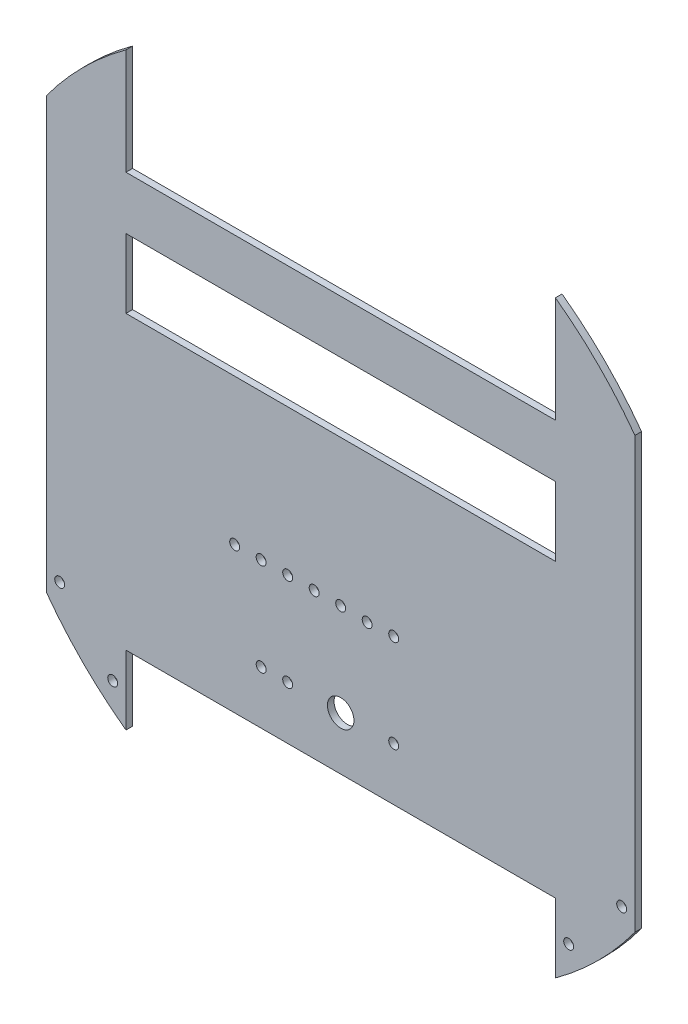
SolidWorks part; units mm, degrees
material "6061 Alloy"
ref_plane "Front Plane" through (0, 0, 0) normal (0, 0, 1) x (1, 0, 0)
ref_plane "Top Plane" through (0, 0, 0) normal (0, 1, 0) x (1, 0, 0)
ref_plane "Right Plane" through (0, 0, 0) normal (1, 0, 0) x (0, 0, -1)
sketch "Sketch1" plane through (0, 0, 0) normal (0, 0, 1) x (1, 0, 0)
  line L1 (-140.9655, 145.0225) -> (-102.8655, 145.0225)
  line L2 (-140.9655, 145.0225) -> (-140.9655, -145.0225)
  line L3 (-140.9655, -145.0225) -> (-102.8655, -145.0225)
  line L4 (-102.8655, 145.0225) -> (-102.8655, -145.0225)
  line L5 (-140.9655, 145.0225) -> (-102.8655, -145.0225) construction
  line L6 (-140.9655, -145.0225) -> (-102.8655, 145.0225) construction
  line L7 (-140.9655, 31.75) -> (140.9655, 31.75)
  line L8 (-140.9655, 31.75) -> (-140.9655, -31.75)
  line L9 (-140.9655, -31.75) -> (140.9655, -31.75)
  line L10 (140.9655, 31.75) -> (140.9655, -31.75)
  line L11 (-140.9655, 31.75) -> (140.9655, -31.75) construction
  line L12 (-140.9655, -31.75) -> (140.9655, 31.75) construction
  line L13 (102.8655, 145.0225) -> (140.9655, 145.0225)
  line L14 (102.8655, 145.0225) -> (102.8655, -145.0225)
  line L15 (102.8655, -145.0225) -> (140.9655, -145.0225)
  line L16 (140.9655, 145.0225) -> (140.9655, -145.0225)
  line L17 (102.8655, 145.0225) -> (140.9655, -145.0225) construction
  line L18 (102.8655, -145.0225) -> (140.9655, 145.0225) construction
  line L19 (-140.9655, -31.75) -> (140.9655, -31.75)
  line L20 (-140.9655, -31.75) -> (-140.9655, -69.85)
  line L21 (-140.9655, -69.85) -> (140.9655, -69.85)
  line L22 (140.9655, -31.75) -> (140.9655, -69.85)
  circle A0 centre (0, 0) radius 177.8
  circle A7 centre (0, -38.1) radius 25.4 construction
  circle A8 centre (-25.4, -38.1) radius 2.3813
  circle A9 centre (25.4, -38.1) radius 2.3813
  circle A10 centre (0, -38.1) radius 2.3812
  point P3 (-121.9155, 0)
  point P12 (121.9155, 0)
  dimension "D1" = 355.6
  dimension "D5" = 50.8
  dimension "D6" = 38.1
  dimension "D7" = 281.9311
  dimension "D10" = 4.7625
  dimension "D8" = 4.7625
  dimension "D9" = 4.7625
  dimension "D2" = 38.1
  dimension "D3" = 38.1
  dimension "D4" = 63.5
  dimension "D12" = 38.1
extrude "Boss-Extrude1" add sketch "Sketch1" along normal blind 3.175 contours L4 A0 L2 L7 | L2 L9 L4 L7 | L14 L7 L4 L9 A8 | L2 A0 L4 L9 | L16 A0 L14 L7 | L7 L14 L9 L10 | L14 A0 L16 L9 | L19 A10 L9 L4 L21 L14 A9 A8 | L2 L21 L4 L9 | L14 L21 L16 L9 region at (-120.723, 80.7079, 0) region at (0, 0, 0) region at (-121.9155, 0, 0) region at (120.723, 80.7079, 0) region at (-119.9486, -100.1295, 0) region at (0, -50.8872, 0) region at (-121.9155, -50.8, 0) region at (121.9155, 0, 0) region at (121.9155, -50.8, 0) region at (119.9486, -100.1295, 0)
sketch "Sketch2" plane through (0, 0, 3.175) normal (0, 0, 1) x (1, 0, 0)
  line L0 (-140.9655, -103.066) -> (-140.9655, -108.3585)
  line L1 (-140.9655, 108.3585) -> (-140.9655, -108.3585) construction
  line L2 (-102.8655, -141.1119) -> (-102.8655, -145.0225)
  line L3 (102.8655, -141.1119) -> (102.8655, -145.0225)
  line L4 (102.8655, -69.85) -> (102.8655, -145.0225) construction
  line L5 (140.9655, -103.066) -> (140.9655, -108.3585)
  line L6 (140.9655, 108.3585) -> (140.9655, -108.3585) construction
  line L7 (-102.8655, -69.85) -> (-102.8655, -145.0225) construction
  circle A0 centre (0, 0) radius 177.8
  circle A1 centre (0, 0) radius 174.625
  line M3 (-140.9655, 108.3585) -> (-140.9655, -108.3585)
  arc M4 (-140.9655, -108.3585) -> (-102.8655, -145.0225) centre (0, 0) ccw
  line M5 (-102.8655, -145.0225) -> (-102.8655, -69.85)
  line M7 (102.8655, -69.85) -> (102.8655, -145.0225)
  arc M8 (102.8655, -145.0225) -> (140.9655, -108.3585) centre (0, 0) ccw
  line M9 (140.9655, -108.3585) -> (140.9655, 108.3585)
  dimension "D1" = 355.6
  dimension "D2" = 349.25
extrude "Boss-Extrude2" add sketch "Sketch2" along normal blind 50.8 contours A1 M3 M4 M5 | A1 M7 M8 M9 region at (-122.8631, -125.3578, 3.175) region at (122.8631, -125.3578, 3.175)
sketch "Sketch3" plane through (0, 0, 3.175) normal (0, 0, 1) x (1, 0, 0)
  circle A0 centre (0, 0) radius 174.625
  circle A1 centre (0, 0) radius 203.8293
  dimension "D1" = 349.25
extrude "Cut-Extrude1" cut sketch "Sketch3" along normal through all and the other way through all
sketch "Sketch5" plane through (0, 0, 3.175) normal (0, 0, 1) x (1, 0, 0)
  line L0 (0, 165.1) -> (0, -165.1) construction
  line L1 (102.8655, -69.85) -> (102.8655, -141.1119) construction
  circle A0 centre (0, 0) radius 165.1 construction
  circle A1 centre (134.6155, -95.5859) radius 2.3813
  circle A2 centre (109.2155, -123.8143) radius 2.3813
  circle A3 centre (-134.6155, -95.5859) radius 2.3813
  circle A4 centre (-109.2155, -123.8143) radius 2.3813
  arc A5 (140.9655, 103.066) -> (102.8655, 141.1119) centre (0, 0) ccw construction
  dimension "D1" = 330.2
  dimension "D3" = 4.7625
  dimension "D4" = 4.7625
  dimension "D2" = 25.4
  dimension "D5" = 6.35
extrude "Cut-Extrude3" cut sketch "Sketch5" against normal through all
sketch "Sketch6" plane through (0, 0, 3.175) normal (0, 0, 1) x (1, 0, 0)
  line L0 (-102.8655, 141.1119) -> (-102.8655, 31.75) construction
  line L1 (-102.8655, 90.3119) -> (102.8655, 90.3119)
  line L2 (-102.8655, 90.3119) -> (-102.8655, 64.9119)
  line L3 (-102.8655, 64.9119) -> (102.8655, 64.9119)
  line L4 (102.8655, 90.3119) -> (102.8655, 64.9119)
  line L5 (102.8655, 141.1119) -> (102.8655, 31.75) construction
  dimension "D1" = 25.4
  dimension "D2" = 50.8
extrude "Boss-Extrude3" add sketch "Sketch6" against normal blind 3.175
sketch "Sketch7" plane through (0, 0, 3.175) normal (0, 0, 1) x (1, 0, 0)
  line L0 (102.8655, 90.3119) -> (-102.8655, 90.3119) construction
  line L1 (-157.8266, 90.3119) -> (153.0605, 90.3119)
  line L2 (-157.8266, 90.3119) -> (-157.8266, 162.3702)
  line L3 (-157.8266, 162.3702) -> (153.0605, 162.3702)
  line L4 (153.0605, 90.3119) -> (153.0605, 162.3702)
extrude "Cut-Extrude4" [suppressed] cut sketch "Sketch7" against normal through all
sketch "Sketch8" plane through (0, 0, 3.175) normal (0, 0, 1) x (1, 0, 0)
  circle A0 centre (0, -38.1) radius 38.1 construction
  circle A1 centre (-38.1, -38.1) radius 2.3812
  circle A2 centre (0, -38.1) radius 50.8 construction
  circle A3 centre (-50.8, -38.1) radius 2.3812
  circle A4 centre (0, -38.1) radius 12.7 construction
  circle A5 centre (12.6884, -38.6427) radius 2.3812
  circle A6 centre (-12.7, -38.1) radius 2.3812
  dimension "D1" = 76.2
  dimension "D2" = 4.7625
  dimension "D3" = 101.6
  dimension "D4" = 4.7625
  dimension "D5" = 25.4
  dimension "D6" = 4.7625
  dimension "D7" = 4.7625
extrude "Cut-Extrude5" cut sketch "Sketch8" against normal through all
sketch "Sketch9" plane through (0, 0, 3.175) normal (0, 0, 1) x (1, 0, 0)
  line L0 (102.8655, -69.85) -> (102.8655, -141.1119) construction
  line L1 (-102.8655, -69.85) -> (102.8655, -69.85)
  line L2 (-102.8655, -69.85) -> (-102.8655, -107.95)
  line L3 (-102.8655, -107.95) -> (102.8655, -107.95)
  line L4 (102.8655, -69.85) -> (102.8655, -107.95)
  dimension "D1" = 38.1
extrude "Boss-Extrude4" add sketch "Sketch9" against normal blind 3.175
sketch "Sketch10" plane through (0, 0, 3.175) normal (0, 0, 1) x (1, 0, 0)
  circle A0 centre (0, -82.55) radius 6.35
  circle A1 centre (0, -38.1) radius 2.3812 construction
  circle A2 centre (0, -82.55) radius 25.4 construction
  circle A3 centre (0, -82.55) radius 38.1 construction
  circle A4 centre (-25.4, -82.55) radius 2.3813
  circle A5 centre (-38.1, -82.55) radius 2.3812
  circle A6 centre (25.4, -82.55) radius 2.3813
  dimension "D1" = 44.45
  dimension "D2" = 12.7
  dimension "D3" = 50.8
  dimension "D4" = 76.2
  dimension "D5" = 4.7625
  dimension "D6" = 4.7625
  dimension "D7" = 4.7625
extrude "Cut-Extrude6" cut sketch "Sketch10" against normal through all
